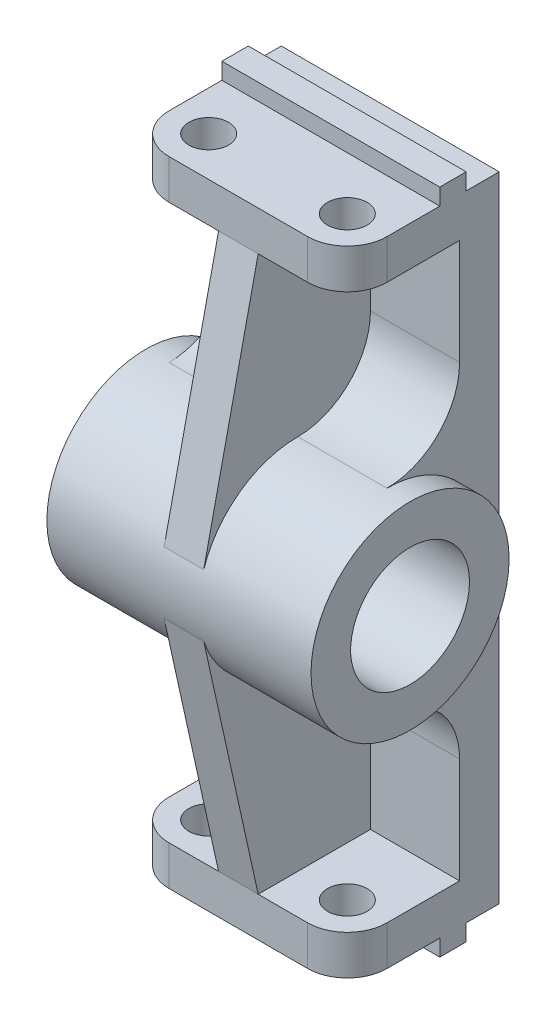
SolidWorks part; units mm, degrees
ref_plane "Front Plane" through (0, 0, 0) normal (1, 0, 0) x (0, 1, 0)
ref_plane "Top Plane" through (0, 0, 0) normal (0, 0, 1) x (0, 1, 0)
ref_plane "Right Plane" through (0, 0, 0) normal (0, 1, 0) x (-1, 0, 0)
sketch "Sketch1" plane through (0, 0, 0) normal (1, 0, 0) x (0, 1, 0)
  line L0 (-96, -34) -> (96, -34)
  line L1 (-84, -22) -> (84, -22)
  line L2 (-96, -34) -> (-96, -24)
  line L3 (-96, -24) -> (-101, -24)
  line L4 (-101, -24) -> (-101, -16)
  line L5 (-101, -16) -> (-96, -16)
  line L6 (-96, -16) -> (-96, 12)
  line L7 (-96, 12) -> (-84, 12)
  line L8 (-84, 12) -> (-84, -22)
  line L9 (0, 0) -> (0, 50.6904) construction
  line L10 (96, -34) -> (96, -24)
  line L11 (96, -24) -> (101, -24)
  line L12 (101, -24) -> (101, -16)
  line L13 (101, -16) -> (96, -16)
  line L14 (96, -16) -> (96, 12)
  line L15 (84, 12) -> (84, -22)
  line L16 (96, 12) -> (84, 12)
  circle A0 centre (0, 0) radius 30
  circle A1 centre (0, 0) radius 18
  point P6 (0, -34)
  point P9 (0, -22)
  dimension "D1" = 60
  dimension "D2" = 36
  dimension "D3" = 34
  dimension "D4" = 192
  dimension "D5" = 12
  dimension "D6" = 12
  dimension "D7" = 10
  dimension "D8" = 8
  dimension "D9" = 46
  dimension "D10" = 202
extrude "Boss-Extrude1" add sketch "Sketch1" along normal mid plane 66 contours A0 L1 L8 L7 L6 L5 L4 L3 L2 L0 L10 L11 L12 L13 L14 L16 L15 region at (0, -93.9283, -29)
extrude "Boss-Extrude2" add sketch "Sketch1<3>" along normal mid plane 80 contours A1 A0 L1 | A0 region at (0, -11.6848, 26.7667)
sketch "Sketch1<3>" plane through (0, 0, 0) normal (1, 0, 0) x (0, 1, 0) same geometry as "Sketch1"
fillet "Fillet1" radius 22 2 edges at (0, -20.3961, -22) (0, 20.3961, -22)
sketch "Sketch2" plane through (0, 0, 0) normal (1, 0, 0) x (0, 1, 0)
  line L0 (-84, 12) -> (-9.3905, 28.4924)
  circle A0 centre (0, 0) radius 30 construction
rib "Rib1" sketch "Sketch2" sketch "Sketch2" thickness 12 extrusion direction parallel to sketch draft on no parameters "D1"=12
mirror "Mirror1" about plane through (0, 0, 0) normal (0, 1, 0) of "Rib1"
fillet "Fillet2" radius 12 4 edges at (-33, -90, 12) (-33, 90, 12) (33, -90, 12) (33, 90, 12)
sketch "Sketch3" plane through (0, 96, 0) normal (0, 1, 0) x (-1, 0, 0)
  line L0 (0, 0) -> (0, -11.3027) construction
  circle A0 centre (-21, 0) radius 6
  circle A1 centre (21, 0) radius 6
  arc A2 (-21, 12) -> (-33, 0) centre (-21, 0) ccw construction
  dimension "D1" = 12
extrude "Cut-Extrude1" cut sketch "Sketch3" against normal up to surface (12 mm away) up to face at (20.2971, 84, -3.5029)
sketch "Sketch4" plane through (0, -96, 0) normal (0, -1, 0) x (1, 0, 0)
  circle A0 centre (-21, 0) radius 6
  circle A1 centre (21, 0) radius 6
  dimension "D1" = 12
extrude "Cut-Extrude2" cut sketch "Sketch4" against normal up to surface (12 mm away) up to face at (-20.2971, -84, -3.5029)
sketch "Sketch5" plane through (40, 0, 0) normal (1, 0, 0) x (0, 1, 0)
  circle A0 centre (0, 0) radius 18
  dimension "D1" = 36
extrude "Cut-Extrude3" cut sketch "Sketch5" against normal up to surface (80 mm away) up to face at (-40, 0, -30)
